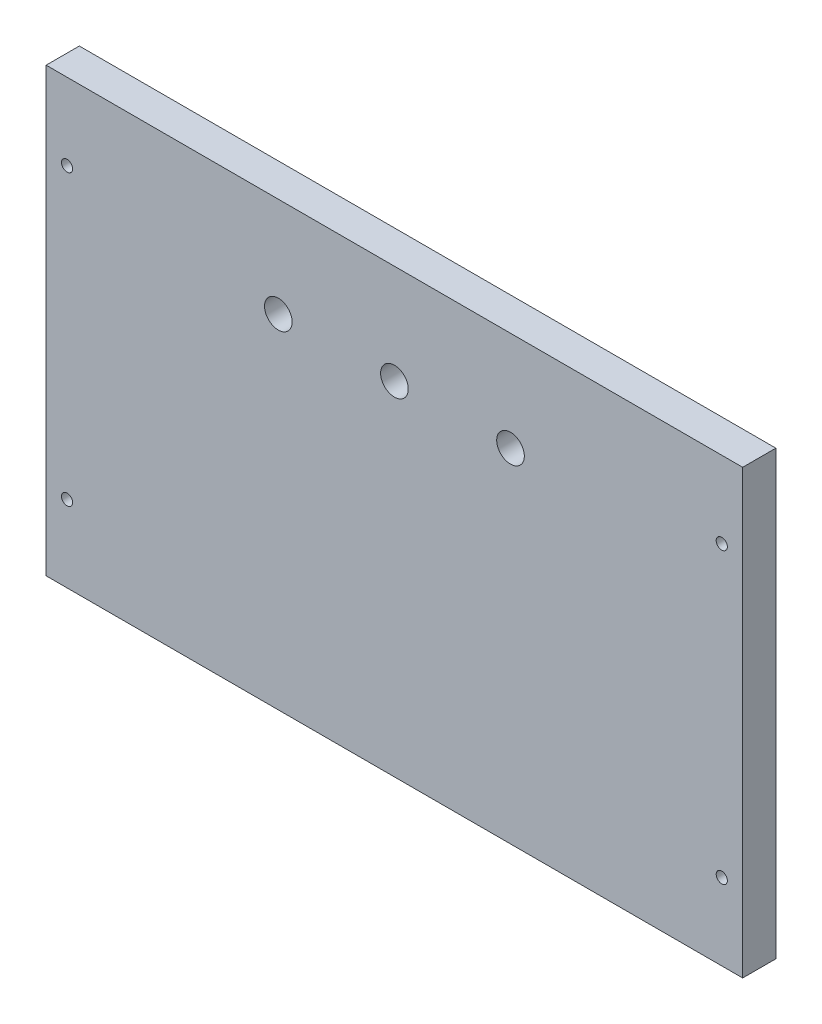
SolidWorks part; units mm, degrees
ref_plane "Front Plane" through (0, 0, 0) normal (0, 0, 1) x (1, 0, 0)
ref_plane "Top Plane" through (0, 0, 0) normal (0, 1, 0) x (1, 0, 0)
ref_plane "Right Plane" through (0, 0, 0) normal (1, 0, 0) x (0, 0, -1)
sketch "Sketch1" plane through (0, 0, 0) normal (0, 0, 1) x (1, 0, 0)
  line L0 (100, 127) -> (100, 98.425) construction
  line L1 (0, 0) -> (200, 0)
  line L2 (0, 0) -> (0, 127)
  line L3 (0, 127) -> (200, 127)
  line L4 (200, 0) -> (200, 127)
  line L5 (66.6667, 127) -> (66.6667, 98.425) construction
  line L6 (133.3333, 127) -> (133.3333, 98.425) construction
  circle A0 centre (66.6667, 98.425) radius 3.9687
  circle A1 centre (100, 98.425) radius 3.9687
  circle A2 centre (133.3333, 98.425) radius 3.9687
  circle A3 centre (6, 105) radius 1.6
  circle A4 centre (6, 22) radius 1.6
  circle A5 centre (194, 22) radius 1.6
  circle A6 centre (194, 105) radius 1.6
  dimension "D3" = 7.9375
  dimension "D4" = 7.9375
  dimension "D5" = 7.9375
  dimension "D11" = 3.2
  dimension "D14" = 3.2
  dimension "D17" = 3.2
  dimension "D22" = 3.2
  dimension "D1" = 127
  dimension "D2" = 200
  dimension "D6" = 28.575
  dimension "D7" = 28.575
  dimension "D8" = 28.575
  dimension "D9" = 66.6667
  dimension "D10" = 66.6667
  dimension "D12" = 6
  dimension "D13" = 22
  dimension "D15" = 6
  dimension "D16" = 22
  dimension "D18" = 6
  dimension "D19" = 22
  dimension "D20" = 6
  dimension "D21" = 22
extrude "Boss-Extrude1" add sketch "Sketch1" along normal blind 9.525
equation "\"Length\"= 283mm"
equation "\"Width\"= 225mm"
equation "\"WallThickness\"= 12.5mm"
equation "\"UpperWaterJacketThickness\"= 28mm"
equation "\"SpacerHeight\"= 80.2mm"
equation "\"SpacerCornerWidth\"= 10mm"
equation "\"SpacerCornerHeight\"= 60.16mm"
equation "\"SpacerPegDiameter\"= 10mm"
equation "\"SpacerPegHeight\"= 10mm"
equation "\"TubingShort\"= 110mm"
equation "\"TubingLong\"= 175mm"
equation "\"PlateLength\"= 252mm"
equation "\"PlateWidth\"= 190mm"
equation "\"PlateHoleDiameter\"= 5.9mm"
equation "\"PlateHoleBottom\"= 2mm"
equation "\"PlateHoleSide\"= 1.55mm"
equation "\"PlateHoleSpacing\"= 3.1mm"
equation "\"PlateThickness\"= 1.55mm"
equation "\"ReservoirBottom\"= 12.5mm"
equation "\"ReservoirSupportWidth\"= 12mm"
equation "\"ReservoirSupportHeight\"= 15.1mm"
equation "\"ReservoirSupportPlacementHeight\"= 50mm"
equation "\"ReservoirHoleDiameter\"= 12.7mm"
equation "\"ReservoirHoleRight\"= 25mm"
equation "\"ReservoirHoleTop\"= \"ReservoirSupportPlacementHeight\""
equation "\"ReservoirHeight\"= 90mm"
equation "\"ReservoirPortBottom\"= 4mm"
equation "\"ReservoirPortTop\"= 10mm"
equation "\"ReservoirPortWidth\"= 101mm"
equation "\"CustomSpacerWallThickness\" = 0.375in"
equation "\"CustomSpacerHeight\"= 5in"
equation "\"CustomSpacerRodHoleHeight\"= .75in"
equation "\"CustomSpacerRodHoleDiameter\"= .3125in"
equation "\"ScrewBlockSide\"= 12mm"
equation "\"ScrewBlockUpperHeight\"= 16mm"
equation "\"ScrewBlockLowerHeight\"= 16mm"
equation "\"InternalLength\"= \"Length\" - ( 2 * \"WallThickness\" )"
equation "\"InternalWidth\"= \"Width\" - ( 2 * \"WallThickness\" )"
equation "\"CustomSpacerPegHeight\"= 1in"
equation "\"CustomSpacerScrewBore\"=3.2mm"
equation "\"CustomSpacerScrewDepth\"=10mm"
equation "\"D1@Sketch1\"=\"CustomSpacerHeight\""
equation "\"D2@Sketch1\"=\"InternalWidth\""
equation "\"D3@Sketch1\"=\"CustomSpacerRodHoleDiameter\""
equation "\"D4@Sketch1\"=\"CustomSpacerRodHoleDiameter\""
equation "\"D5@Sketch1\"=\"CustomSpacerRodHoleDiameter\""
equation "\"D6@Sketch1\"=\"CustomSpacerRodHoleHeight\"+\"CustomSpacerRodHoleDiameter\"+0.0625in"
equation "\"D7@Sketch1\"=\"CustomSpacerRodHoleHeight\"+\"CustomSpacerRodHoleDiameter\"+0.0625in"
equation "\"D8@Sketch1\"=\"CustomSpacerRodHoleHeight\"+\"CustomSpacerRodHoleDiameter\"+0.0625in"
equation "\"D9@Sketch1\"=\"InternalWidth\"/3"
equation "\"D10@Sketch1\"=\"InternalWidth\"/3"
equation "\"D11@Sketch1\"=\"CustomSpacerScrewBore\""
equation "\"D12@Sketch1\"=\"ScrewBlockSide\"/2"
equation "\"D13@Sketch1\"=\"ScrewBlockUpperHeight\"+\"ScrewBlockSide\"/2"
equation "\"D14@Sketch1\"=\"CustomSpacerScrewBore\""
equation "\"D15@Sketch1\"=\"ScrewBlockSide\"/2"
equation "\"D16@Sketch1\"=\"ScrewBlockLowerHeight\"+\"ScrewBlockSide\"/2"
equation "\"D17@Sketch1\"=\"CustomSpacerScrewBore\""
equation "\"D18@Sketch1\"=\"ScrewBlockSide\"/2"
equation "\"D19@Sketch1\"=\"ScrewBlockUpperHeight\"+\"ScrewBlockSide\"/2"
equation "\"D20@Sketch1\"=\"ScrewBlockSide\"/2"
equation "\"D21@Sketch1\"=\"ScrewBlockLowerHeight\"+\"ScrewBlockSide\"/2"
equation "\"D22@Sketch1\"=\"CustomSpacerScrewBore\""
equation "\"D1@Boss-Extrude1\"=\"CustomSpacerWallThickness\""
